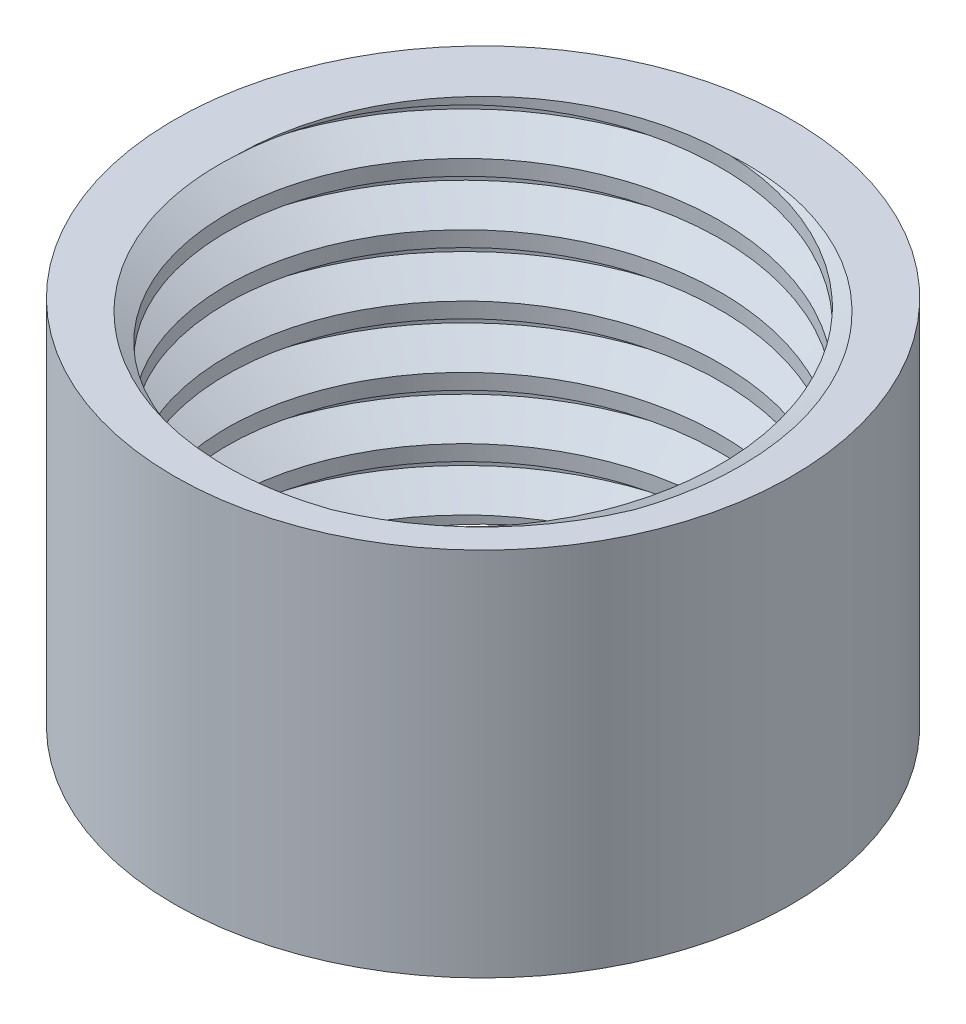
SolidWorks part; units mm, degrees
ref_plane "Front Plane" through (0, 0, 0) normal (0, 0, 1) x (1, 0, 0)
ref_plane "Top Plane" through (0, 0, 0) normal (0, 1, 0) x (1, 0, 0)
ref_plane "Right Plane" through (0, 0, 0) normal (1, 0, 0) x (0, 0, -1)
ref_axis "X" through (-88.99, 0, 0) along (1, 0, 0)
ref_axis "Y" through (0, 55, 0) along (0, -1, 0)
ref_axis "Z" through (0, 0, -88.99) along (0, 0, 1)
sketch "Sketch1" plane through (0, 0, 0) normal (0, 1, 0) x (1, 0, 0)
  circle A0 centre (0, 0) radius 5
  circle A1 centre (0, 0) radius 4
  dimension "D1" = 10
  dimension "D2" = 1
extrude "Boss-Extrude1" add sketch "Sketch1" along normal blind 6
thread "Thread1" pitch 1 method cut profile "Thread Profile1" start angle 0, offset 1, length 0, pitch 1, diameter 8
ref_plane "Plane1" through (-4, 7, 0) normal (0, 0, 1) x (-1, 0, 0)
sketch "Thread Profile1" plane through (-4, 7, 0) normal (0, 0, 1) x (-1, 0, 0)
  line L0 (0, 0) -> (0, 1) construction
  line L1 (0, 0) -> (0.5413, 0.3125)
  line L2 (0.5413, 0.3125) -> (0.5413, 0.4375)
  line L3 (0.5413, 0.4375) -> (0, 0.75)
  line L4 (0.5413, 0.375) -> (0, 0.375) construction
  line L11 (0, 0) -> (0, 0.75)
  point P2 (0, 0)
  dimension "Pitch" = 1
  dimension "Profile_Angle" = 60
  dimension "Profile_Land" = 0.125
  dimension "Profile_Height" = 0.5413
